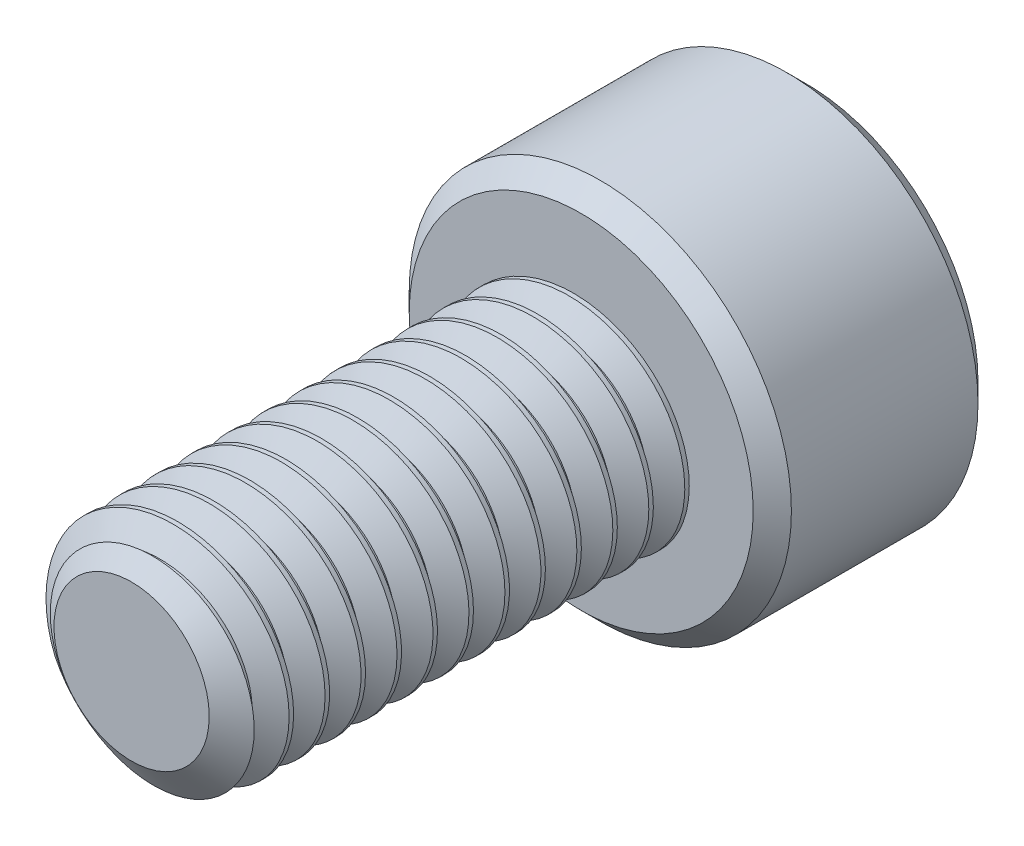
SolidWorks part; units mm, degrees
note: '?' marks a value the reader was unsure of.
ref_plane "xy_plane" through (0, 0, 0) normal (0, 0, 1) x (1, 0, 0)
ref_plane "zx_plane" through (0, 0, 0) normal (0, 1, 0) x (1, 0, 0)
ref_plane "yz_plane" through (0, 0, 0) normal (1, 0, 0) x (0, 0, -1)
ref_axis "x_axis" through (-4.675, 0, 0) along (1, 0, 0)?
ref_axis "y_axis" through (0, -4.675, 0) along (0, 1, 0)?
ref_axis "z_axis" through (0, 0, -14.84) along (0, 0, 1)?
sketch "Sketch1" plane through (0, 0, 0) normal (0, 0, 1) x (1, 0, 0)
  circle A0 centre (0, 0) radius 2.5
  dimension "OD" = 5
extrude "Extrude1" add sketch "Sketch1" against normal blind 10
sketch "Sketch2" plane through (0, 0, 0) normal (0, 0, 1) x (1, 0, 0)
  circle A0 centre (0, 0) radius 2.5 construction
  circle A1 centre (0, 0) radius 2.5
curve "Helix/Spiral1" pitch 0.8 height 10.8 turns 13.5 parameters "pitch"=0.8
sketch "Sketch3" plane through (0, 0, 0) normal (1, 0, 0) x (0, 0, -1)
  line L0 (-0.7, 2.5) -> (-0.4, 1.9804)
  line L1 (-0.4, 1.9804) -> (-0.3, 1.9804)
  line L2 (-0.3, 1.9804) -> (0, 2.5)
  line L3 (-0.7, 2.5) -> (0, 2.5)
  line L4 (-0.35, 2.5) -> (-0.35, 1.9804) construction
  line L5 (-0.55, 2.2402) -> (-0.15, 2.2402) construction
  line L6 (0, 2.5) -> (0, -2.5) construction
  dimension "D1" = 0.1
  dimension "D2" = 0.4
  dimension "D3" = 60
sweep "Cut-Sweep1" cut profiles "Sketch3" path "Helix/Spiral1"
sketch "Sketch4" plane through (0, 0, 0) normal (1, 0, 0) x (0, 0, -1)
  line L0 (0.5417, 2.5) -> (0, 1.7264)
  line L1 (0, 1.7264) -> (0, 2.5)
  line L2 (0.5417, 2.5) -> (0, 2.5)
  line L3 (-0.7, 2.5) -> (0, 2.5) construction
  line L4 (0, 0) -> (7.0209, 0) construction
  dimension "D1" = 55
  dimension "D2" = 0.254
revolve "Cut-Revolve1" cut sketch "Sketch4" angle 360 about L4
sketch "Sketch6" plane through (0, 0, -10) normal (0, 0, -1) x (-1, 0, 0)
  circle A0 centre (0, 0) radius 4.25
  dimension "head dia" = 8.5
extrude "Extrude2" add sketch "Sketch6" along normal blind 5
sketch "Sketch7" plane through (0, 0, -15) normal (0, 0, -1) x (-1, 0, 0)
  line L1 (0, 2.3094) -> (-2, 1.1547)
  line L2 (-2, 1.1547) -> (-2, -1.1547)
  line L3 (-2, -1.1547) -> (0, -2.3094)
  line L4 (0, -2.3094) -> (2, -1.1547)
  line L5 (2, -1.1547) -> (2, 1.1547)
  line L6 (2, 1.1547) -> (0, 2.3094)
  circle A0 centre (0, 0) radius 2 construction
  dimension "hex dia" = 4
extrude "Cut-Extrude1" cut sketch "Sketch7" against normal blind 3
sketch "Sketch8" plane through (0, 0, -15) normal (0, 0, -1) x (-1, 0, 0)
  circle A0 centre (0, 0) radius 2.3094
extrude "Cut-Extrude2" cut sketch "Sketch8" against normal through all draft 45
chamfer "Chamfer1" distance 0.425 angle 45 2 edges at (-4.25, 0, -15) (-4.25, 0, -10)
sketch "Sketch10" plane through (0, 0, -10) normal (0, 0, 1) x (1, 0, 0)
  circle A1 centre (0, 0) radius 2.5
  circle A2 centre (0, 0) radius 2.5
  dimension "D1" = 0
ref_plane "Plane1" through (0, 0, 0) normal (0, 0, 1) x (1, 0, 0)
extrude "partial thread" [suppressed] add sketch "Sketch10" along normal up to surface (13 mm away) separate body
chamfer "Chamfer2" [suppressed] distance 0.1 angle 45
combine bodies "Combine1" [suppressed] operation type add bodies to combine 107 108
sketch "Sketch9" plane through (0, 0, 0) normal (1, 0, 0) x (0, 0, -1)
  line L0 (0, 2.5) -> (0, -2.5) construction
  line L1 (2, 2.5) -> (2, -2.5) construction
  dimension "D1" = 2
equation "\"D3@Helix/Spiral1\" = \"screw length@Extrude1\"+\"pitch@Helix/Spiral1\""
equation "\"D1@Sketch3\" = \"pitch@Helix/Spiral1\"*.125"
equation "\"D2@Sketch3\" = \"pitch@Helix/Spiral1\"*.5"
equation "\"D1@Cut-Extrude1\" = \"hex dia@Sketch7\"*.75"
equation "\"D1@Chamfer1\" = \"head dia@Sketch6\"*.05"
equation "\"D1@Sketch9\" = \"pitch@Helix/Spiral1\"*2.5"
equation "\"D1@Chamfer2\"=\"OD@Sketch1\"*.02"
equation "\"screw length@Extrude1\"= \"externalParameters.this.length\""
